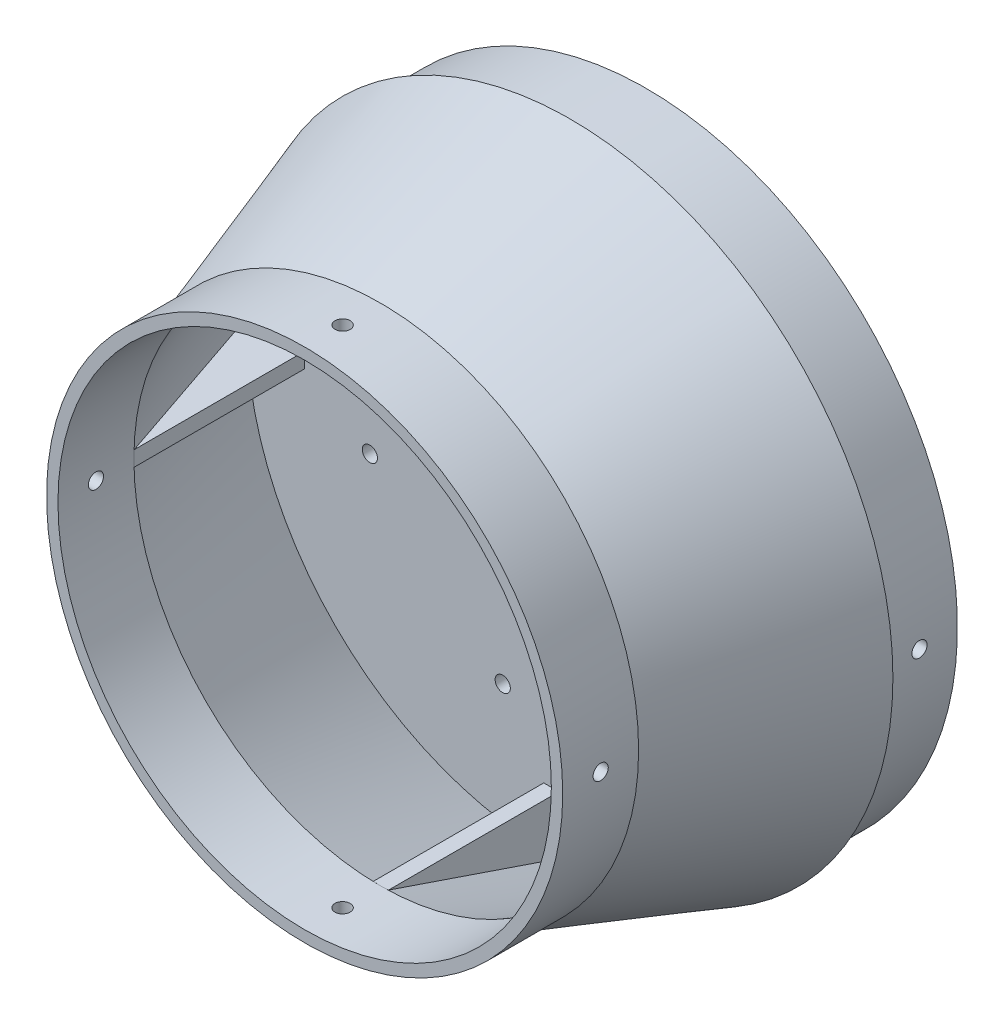
SolidWorks part; units mm, degrees
ref_plane "Front Plane" through (0, 0, 0) normal (0, 0, 1) x (1, 0, 0)
ref_plane "Top Plane" through (0, 0, 0) normal (0, 1, 0) x (1, 0, 0)
ref_plane "Right Plane" through (0, 0, 0) normal (1, 0, 0) x (0, 0, -1)
sketch "Sketch10" plane through (0, 0, 0) normal (0, 1, 0) x (1, 0, 0)
  line L9 (68, 0) -> (85, 50)
  line L10 (65, 0) -> (65, -20)
  line L11 (65, -20) -> (68, -20)
  line L12 (68, -20) -> (68, 0)
  line L13 (85, 50) -> (0, 50)
  line L14 (0, 50) -> (0, 45)
  line L16 (0, 0) -> (0, 90.5218) construction
  line L17 (65, 0) -> (80.3, 45)
  line L18 (0, 45) -> (80.3, 45)
  dimension "D1" = 65
  dimension "D2" = 20
  dimension "D3" = 50
  dimension "D4" = 85
  dimension "D5" = 68
  dimension "D6" = 5
revolve "Revolve2" add sketch "Sketch10" angle 360 about L16
sketch "Sketch12" plane through (0, 0, 0) normal (0, 1, 0) x (1, 0, 0)
  line L4 (-80.3, 45) -> (-65, 0)
  line L5 (-65, 0) -> (-65, 45)
  line L6 (-80.3, 45) -> (80.3, 45) construction
  line L7 (-65, 45) -> (-80.3, 45)
extrude "Boss-Extrude5" add sketch "Sketch12" along normal blind 2 and the other way blind 2
pattern_circular "CirPattern3" count 4 every 90 about axis through (0, 0, -50) along (0, 0, 1) of "Boss-Extrude5"
sketch "Sketch13" plane through (0, 0, -50) normal (0, 0, -1) x (-1, 0, 0)
  arc A0 (70, 42.7083) -> (70, -42.7083) centre (0, 0) ccw
  arc A1 (70, 34.4093) -> (70, -34.4093) centre (0, 0) ccw
  circle A2 centre (0, 0) radius 82 construction
  circle A3 centre (0, 0) radius 78 construction
  circle A4 centre (0, 0) radius 82
  circle A5 centre (0, 0) radius 78
  dimension "D1" = 164
  dimension "D2" = 4
extrude "Boss-Extrude6" add sketch "Sketch13" along normal blind 20 contours A0 A4 A5 A1 region at (-76.7102, 21.5537, -50)
sketch "Sketch14" plane through (0, 0, 0) normal (0, 1, 0) x (1, 0, 0)
  line L0 (-65, -20) -> (65, -20) construction
  circle A0 centre (0, -10) radius 2
  dimension "D1" = 4
  dimension "D2" = 10
extrude "Cut-Extrude1" cut sketch "Sketch14" against normal blind 95
pattern_circular "CirPattern4" count 4 every 90 about axis through (0, 0, 20) along (0, 0, 1) of "Cut-Extrude1"
fillet "Fillet1" radius 5 1 edges at (-78, 0, -50)
sketch "Sketch16" plane through (0, 0, 0) normal (0, 1, 0) x (1, 0, 0)
  line L0 (85, 50) -> (-85, 50) construction
  circle A0 centre (0, 60) radius 2
  dimension "D1" = 4
  dimension "D2" = 10
extrude "Cut-Extrude2" cut sketch "Sketch16" against normal blind 94
pattern_circular "CirPattern5" count 2 every 90 about axis through (0, 0, -70) along (0, 0, -1) of "Cut-Extrude2" other way count 2
sketch "Sketch17" plane through (0, 0, -50) normal (0, 0, -1) x (-1, 0, 0)
  line L0 (0, 0) -> (-47.8133, 12.8115) construction
  line L1 (0, 0) -> (-12.8115, 47.8133) construction
  circle A0 centre (-47.8133, 12.8115) radius 2
  circle A4 centre (-12.8115, 47.8133) radius 2
  circle A5 centre (12.8115, -47.8133) radius 2
  circle A6 centre (47.8133, -12.8115) radius 2
  point P12 (0, 0)
  point P16 (0, 0)
  dimension "D1" = 4
  dimension "D2" = 49.5
  dimension "D4" = 60
  dimension "D3" = 2
  dimension "D5" = 2
extrude "Cut-Extrude4" cut sketch "Sketch17" against normal blind 900
